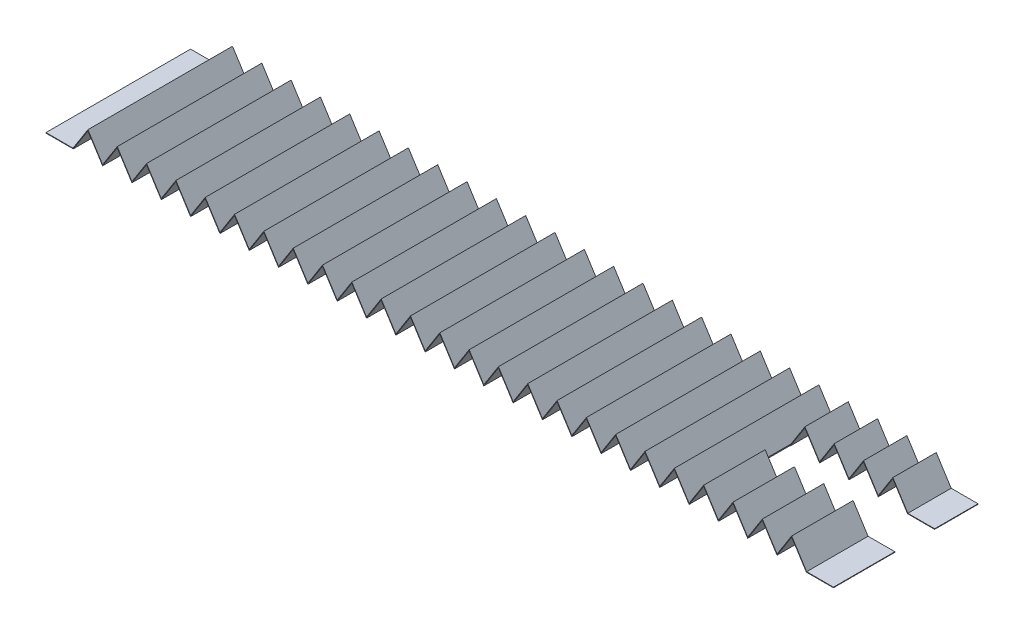
SolidWorks part; units mm, degrees
ref_plane "Front Plane" through (0, 0, 0) normal (0, 0, 1) x (1, 0, 0)
ref_plane "Top Plane" through (0, 0, 0) normal (0, 1, 0) x (1, 0, 0)
ref_plane "Right Plane" through (0, 0, 0) normal (1, 0, 0) x (0, 0, -1)
sketch "Sketch1" plane through (0, 0, 0) normal (0, 0, 1) x (1, 0, 0)
  line L0 (0, 0) -> (8.1143, 12.7345)
  line L1 (8.1143, 12.7345) -> (16.2286, 0)
  line L2 (0, 0) -> (511, 0) construction
  line L3 (16.2286, 0) -> (24.3429, 12.7345)
  line L4 (24.3429, 12.7345) -> (32.4572, 0)
  line L5 (32.4572, 0) -> (40.5715, 12.7345)
  line L6 (40.5715, 12.7345) -> (48.6858, 0)
  line L7 (48.6858, 0) -> (56.8001, 12.7345)
  line L8 (56.8001, 12.7345) -> (64.9144, 0)
  line L9 (64.9144, 0) -> (73.0287, 12.7345)
  line L10 (73.0287, 12.7345) -> (81.143, 0)
  line L11 (81.143, 0) -> (89.2573, 12.7345)
  line L12 (89.2573, 12.7345) -> (97.3716, 0)
  line L13 (97.3716, 0) -> (105.4859, 12.7345)
  line L14 (105.4859, 12.7345) -> (113.6002, 0)
  line L15 (113.6002, 0) -> (121.7145, 12.7345)
  line L16 (121.7145, 12.7345) -> (129.8288, 0)
  line L17 (129.8288, 0) -> (137.9431, 12.7345)
  line L18 (137.9431, 12.7345) -> (146.0574, 0)
  line L19 (0, 0) -> (-15.1, 0)
  line L20 (146.0574, 0) -> (154.1717, 12.7345)
  line L21 (154.1717, 12.7345) -> (162.286, 0)
  line L22 (162.286, 0) -> (170.4003, 12.7345)
  line L23 (170.4003, 12.7345) -> (178.5146, 0)
  line L24 (178.5146, 0) -> (186.6289, 12.7345)
  line L25 (186.6289, 12.7345) -> (194.7432, 0)
  line L26 (194.7432, 0) -> (202.8575, 12.7345)
  line L27 (202.8575, 12.7345) -> (210.9718, 0)
  line L28 (210.9718, 0) -> (219.0861, 12.7345)
  line L29 (219.0861, 12.7345) -> (227.2004, 0)
  line L30 (227.2004, 0) -> (235.3147, 12.7345)
  line L31 (235.3147, 12.7345) -> (243.429, 0)
  line L32 (243.429, 0) -> (251.5433, 12.7345)
  line L33 (251.5433, 12.7345) -> (259.6576, 0)
  line L34 (259.6576, 0) -> (267.7719, 12.7345)
  line L35 (267.7719, 12.7345) -> (275.8862, 0)
  line L36 (275.8862, 0) -> (284.0005, 12.7345)
  line L37 (284.0005, 12.7345) -> (292.1148, 0)
  line L39 (292.1148, 0) -> (300.2291, 12.7345)
  line L40 (300.2291, 12.7345) -> (308.3434, 0)
  line L41 (308.3434, 0) -> (316.4577, 12.7345)
  line L42 (316.4577, 12.7345) -> (324.572, 0)
  line L43 (324.572, 0) -> (332.6863, 12.7345)
  line L44 (332.6863, 12.7345) -> (340.8006, 0)
  line L45 (340.8006, 0) -> (348.9149, 12.7345)
  line L46 (348.9149, 12.7345) -> (357.0292, 0)
  line L47 (357.0292, 0) -> (365.1435, 12.7345)
  line L48 (365.1435, 12.7345) -> (373.2578, 0)
  line L49 (373.2578, 0) -> (381.3721, 12.7345)
  line L50 (340.715, -119) -> (340.715, 187) construction
  line L51 (381.3721, 12.7345) -> (389.4864, 0)
  line L52 (389.4864, 0) -> (397.6007, 12.7345)
  line L53 (397.6007, 12.7345) -> (405.715, 0)
  line L54 (405.715, 0) -> (420.715, 0)
  dimension "D1" = 511
  dimension "D2" = 15.1
  dimension "D3" = 15
  dimension "D4" = 16.2286
  dimension "D6" = 80
  dimension "D5" = 25
extrude "Extrude-Thin1" add sketch "Sketch1" along normal mid plane 80 thin thin type one direction reverse wall 0.3
sketch "Sketch2" plane through (0, 0, 0) normal (0, 1, 0) x (1, 0, 0)
  line L1 (340.715, -6) -> (420.715, -6)
  line L2 (340.715, -6) -> (340.715, 16)
  line L3 (340.715, 16) -> (420.715, 16)
  line L4 (420.715, -6) -> (420.715, 16)
  line L5 (340.715, -6) -> (420.715, 16) construction
  line L6 (340.715, 16) -> (420.715, -6) construction
  line L8 (420.715, -40) -> (420.715, 40) construction
  point P0 (380.715, 5)
  dimension "D1" = 80
  dimension "D2" = 22
  dimension "D3" = 5
extrude "Cut-Extrude4" cut sketch "Sketch2" against normal through all and the other way through all contours L1 L4 L3 L2 region at (380.715, 0, -5)
